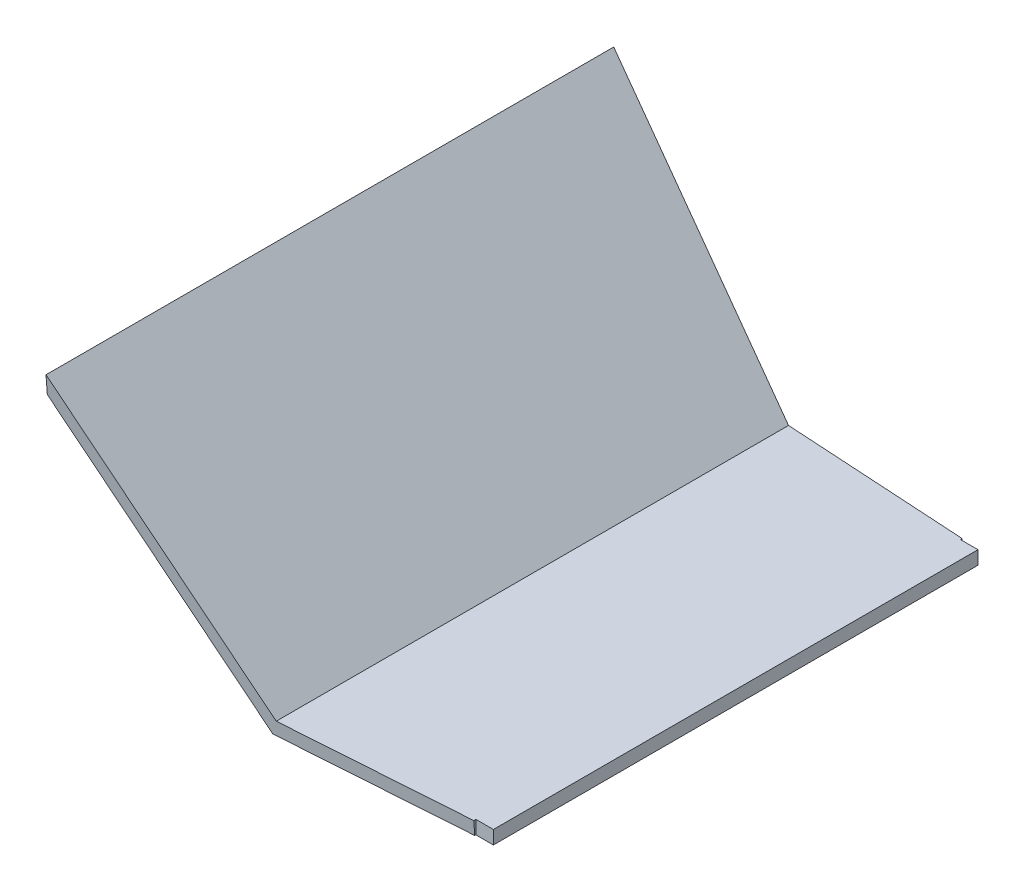
SolidWorks part; units mm, degrees
ref_plane "Front Plane" through (0, 0, 0) normal (0, 0, 1) x (1, 0, 0)
ref_plane "Top Plane" through (0, 0, 0) normal (0, 1, 0) x (1, 0, 0)
ref_plane "Right Plane" through (0, 0, 0) normal (1, 0, 0) x (0, 0, -1)
sketch "Sketch1" plane through (0, 0, 0) normal (0, 0, 1) x (1, 0, 0)
  line L0 (-101.2374, 0) -> (0, 0) construction
  line L1 (0, 0) -> (-101.2374, 120.65) construction
  line L2 (-101.2374, 120.65) -> (-101.2374, 0) construction
  line L3 (-101.2374, 120.65) -> (0, 0)
  line L4 (0, 0) -> (0, 120.65)
  line L5 (-101.2374, 120.65) -> (0, 120.65)
  line L7 (-101.2374, 120.65) -> (0, 120.65)
  line L8 (-101.2374, 120.65) -> (-101.2374, 216.5435)
  line L9 (-101.2374, 216.5435) -> (0, 216.5435)
  line L10 (0, 120.65) -> (0, 216.5435)
  dimension "D1" = 50
  dimension "D2" = 120.65
  dimension "D3" = 95.8935
extrude "Boss-Extrude1" add sketch "Sketch1" along normal blind 5.08 contours L5 L10 L9 L8 | L7 L3 L4 region at (-33.7458, 80.4333, 0) region at (-50.6187, 168.5967, 0)
sketch "Sketch2" plane through (0, 0, 5.08) normal (0, 0, 1) x (1, 0, 0)
  line L0 (-101.2374, 216.5435) -> (0, 108.2717)
  line L1 (0, 0) -> (0, 216.5435) construction
  line L2 (0, 108.2717) -> (0, 216.5435)
  line L3 (0, 216.5435) -> (-101.2374, 216.5435)
extrude "Cut-Extrude1" cut sketch "Sketch2" against normal blind 50.8
sketch "Sketch3" plane through (0, 0, 5.08) normal (0, 0, 1) x (1, 0, 0)
  line L1 (-11.5788, 133.1882) -> (22.7991, 133.1882)
  line L2 (-11.5788, 133.1882) -> (-11.5788, -8.4019)
  line L3 (-11.5788, -8.4019) -> (22.7991, -8.4019)
  line L4 (22.7991, 133.1882) -> (22.7991, -8.4019)
extrude "Cut-Extrude2" cut sketch "Sketch3" against normal blind 25.4
sketch "Sketch4" plane through (0, 0, 0) normal (-0.766, -0.6428, 0) x (0, 0, 1)
  line L0 (2.54, 157.4974) -> (2.54, 18.0134) construction
  line L1 (5.08, 157.4974) -> (0, 157.4974) construction
  line L2 (0, 18.0134) -> (5.08, 18.0134) construction
  circle A0 centre (2.54, 26.4129) radius 1.4224
  circle A1 centre (2.54, 153.4129) radius 1.4224
  dimension "D1" = 127
extrude "Cut-Extrude3" cut sketch "Sketch4" against normal blind 5.08
ref_plane "Plane1" through (0, 0, -63.5) normal (0, 0, -1) x (-1, 0, 0)
sketch "Sketch5" plane through (0, 0, 5.08) normal (0, 0, 1) x (1, 0, 0)
  line L0 (-101.2374, 216.5435) -> (-101.2374, 221.697)
  line L1 (-101.2374, 221.697) -> (-43.1605, 159.6013)
  line L2 (-43.1605, 159.6013) -> (15.4073, 159.6013)
  line L3 (15.4073, 159.6013) -> (15.4073, 155.7023)
  line L4 (15.4073, 155.7023) -> (-44.349, 155.7023)
  line L5 (-101.2374, 216.5435) -> (-11.5788, 120.6551) construction
  line L6 (-44.349, 155.7023) -> (-101.2374, 216.5435)
extrude "Boss-Extrude2" add sketch "Sketch5" against normal blind 164.338
sketch "Sketch6" plane through (0, 0, -63.5) normal (0, 0, -1) x (-1, 0, 0)
  line L0 (11.5788, 120.6551) -> (11.5788, 13.799)
  line L1 (11.5788, 13.799) -> (101.2374, 120.65)
  line L2 (101.2374, 120.65) -> (101.2374, 216.5435)
  line L3 (101.2374, 216.5435) -> (11.5788, 120.6551)
extrude "Cut-Extrude4" cut sketch "Sketch6" against normal blind 152.4
sketch "Sketch7" plane through (56.6003, 52.9371, 0) normal (0.7303, 0.6831, 0) x (0, 0, -1)
  line L0 (-5.08, 231.0685) -> (7.5263, 106.0398)
  line L1 (159.258, 106.0398) -> (-5.08, 106.0398) construction
  line L2 (7.5263, 106.0398) -> (-5.08, 106.0398)
  line L3 (-5.08, 106.0398) -> (-5.08, 231.0685)
  line L4 (159.258, 231.0685) -> (148.2554, 106.0398)
  line L5 (148.2554, 106.0398) -> (159.258, 106.0398)
  line L6 (159.258, 106.0398) -> (159.258, 231.0685)
extrude "Cut-Extrude5" cut sketch "Sketch7" against normal blind 152.4 and the other way blind 152.4
sketch "Sketch8" plane through (15.4073, 0, 0) normal (1, 0, 0) x (0, 0, -1)
  line L1 (-11.2875, 165.3766) -> (7.7789, 165.3766)
  line L2 (-11.2875, 165.3766) -> (-11.2875, 148.002)
  line L3 (-11.2875, 148.002) -> (7.7789, 148.002)
  line L4 (7.7789, 165.3766) -> (7.7789, 148.002)
  line L5 (165.1313, 165.3766) -> (148.0575, 165.3766)
  line L6 (165.1313, 165.3766) -> (165.1313, 148.002)
  line L7 (165.1313, 148.002) -> (148.0575, 148.002)
  line L8 (148.0575, 165.3766) -> (148.0575, 148.002)
extrude "Cut-Extrude6" cut sketch "Sketch8" against normal blind 5.08
